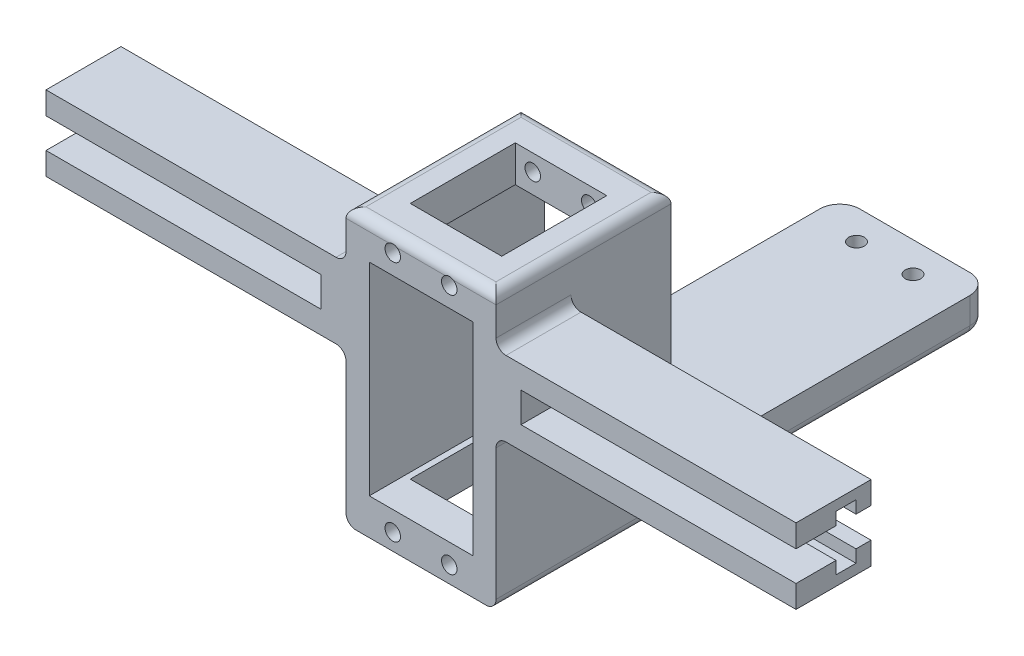
SolidWorks part; units mm, degrees
ref_plane "Front Plane" through (0, 0, 0) normal (0, 0, 1) x (1, 0, 0)
ref_plane "Top Plane" through (0, 0, 0) normal (0, 1, 0) x (1, 0, 0)
ref_plane "Right Plane" through (0, 0, 0) normal (1, 0, 0) x (0, 0, -1)
sketch "Sketch1" plane through (0, 0, 0) normal (0, 0, 1) x (1, 0, 0)
  line L0 (0, 15.3542) -> (0, -15.3542) construction
  line L1 (-15, 27.5) -> (15, 27.5)
  line L2 (-15, 27.5) -> (-15, -27.5)
  line L3 (-15, -27.5) -> (15, -27.5)
  line L4 (15, 27.5) -> (15, -27.5)
  line L5 (-15, 27.5) -> (15, -27.5) construction
  line L6 (-15, -27.5) -> (15, 27.5) construction
  line L7 (11.8315, 0) -> (-11.8315, 0) construction
  line L9 (-10.35, 20.25) -> (10.35, 20.25)
  line L10 (-10.35, 20.25) -> (-10.35, -20.25)
  line L11 (-10.35, -20.25) -> (10.35, -20.25)
  line L12 (10.35, 20.25) -> (10.35, -20.25)
  line L13 (-10.35, 20.25) -> (10.35, -20.25) construction
  line L14 (-10.35, -20.25) -> (10.35, 20.25) construction
  circle A0 centre (5.65, 24.2) radius 1.55
  circle A1 centre (-5.65, 24.2) radius 1.55
  circle A2 centre (-5.65, -24.2) radius 1.55
  circle A3 centre (5.65, -24.2) radius 1.55
  point P0 (0, 0)
  point P11 (0, 0)
  point P14 (0, 0)
  point P20 (0, 0)
  dimension "D3" = 3.1
  dimension "D5" = 11.3
  dimension "D1" = 55
  dimension "D2" = 30
  dimension "D4" = 24.2
  dimension "D6" = 62.6498
  dimension "D7" = 40.5
  dimension "D8" = 20.7
extrude "Boss-Extrude1" add sketch "Sketch1" along normal blind 35
sketch "Sketch4" plane through (0, 0, 0) normal (0, 0, -1) x (-1, 0, 0)
  line L0 (-15, 27.5) -> (15, 27.5) construction
  line L1 (9.15, 20.25) -> (-9.15, 20.25)
  line L2 (9.15, 20.25) -> (9.15, 27.5)
  line L3 (9.15, 27.5) -> (-9.15, 27.5)
  line L4 (-9.15, 20.25) -> (-9.15, 27.5)
  line L5 (-10.35, 20.25) -> (10.35, 20.25) construction
  line L7 (-5.65, 24.2) -> (-5.65, 21.212) construction
  circle A0 centre (5.65, 24.2) radius 1.55 construction
  point P0 (-5.65, 24.2)
  dimension "D1" = 3.5
  dimension "D2" = 3.5
extrude "Cut-Extrude1" [suppressed] cut sketch "Sketch4" against normal offset from surface (21 mm away) 7 from offset 7 offset against normal yes
pattern_linear "LPattern1" [suppressed] count 2 spacing 47.7 of bodies 102
sketch "Sketch11" plane through (0, 0, 0) normal (0, 0, -1) x (-1, 0, 0)
  line L0 (15, 27.5) -> (15, -27.5) construction
  line L1 (-15, -27.5) -> (15, -27.5)
  line L2 (-15, -27.5) -> (-15, -20.25)
  line L3 (-15, -20.25) -> (15, -20.25)
  line L4 (15, -27.5) -> (15, -20.25)
  line L5 (10.35, -20.25) -> (-10.35, -20.25) construction
extrude "Boss-Extrude5" add sketch "Sketch11" along normal blind 63.75
sketch "Sketch12" plane through (0, -27.5, 0) normal (0, -1, 0) x (1, 0, 0)
  line L0 (0, 0) -> (0, -63.75) construction
  line L1 (15, -63.75) -> (-15, -63.75) construction
  circle A0 centre (-5.65, -57.75) radius 1.55
  circle A1 centre (5.65, -57.75) radius 1.55
  dimension "D1" = 3.1
  dimension "D2" = 11.3
  dimension "D3" = 6
extrude "Cut-Extrude2" cut sketch "Sketch12" against normal blind 13
pattern_linear "LPattern2" count 2 spacing 48 along (0, 0, 1) of "Cut-Extrude2"
fillet "Fillet1" radius 4 4 edges at (-12.675, -20.25, 0) (12.675, -20.25, 0) (15, -23.875, -63.75) (-15, -23.875, -63.75)
sketch "Sketch13" plane through (0, 0, 35) normal (0, 0, 1) x (1, 0, 0)
  line L0 (-15, 10.25) -> (15, 10.25) construction
  line L1 (-15, -27.5) -> (15, -27.5) construction
  line L2 (-15, 27.5) -> (-15, -27.5) construction
  line L3 (-15, 27.5) -> (-15, -27.5)
  line L4 (15, -27.5) -> (15, 27.5) construction
  line L5 (0, 0) -> (0, 27.5) construction
  line L6 (-15, 2.75) -> (-75, 2.75)
  line L8 (-15, 17.75) -> (-75, 17.75)
  line L9 (-75, 2.75) -> (-75, 17.75)
  line L10 (-15, 10.25) -> (-75, 17.75) construction
  line L11 (-15, 10.25) -> (-75, 2.75) construction
  line L12 (15, 27.5) -> (-15, 27.5) construction
  line L13 (15, 2.75) -> (75, 2.75)
  line L14 (15, 10.25) -> (75, 2.75) construction
  line L15 (15, 10.25) -> (75, 17.75) construction
  line L16 (75, 2.75) -> (75, 17.75)
  line L17 (15, 17.75) -> (75, 17.75)
  line M12 (15, -27.5) -> (15, 27.5)
  dimension "D1" = 37.75
  dimension "D2" = 60
  dimension "D3" = 15
extrude "Boss-Extrude6" add sketch "Sketch13" against normal blind 15 contours L9 L6 L3 L8 | L17 L13 L16 M12 region at (-45, 10.25, 35) region at (45, 10.25, 35)
sketch "Sketch14" plane through (75, 0, 0) normal (1, 0, 0) x (0, 0, -1)
  line L0 (-35, 10.25) -> (-20, 10.25) construction
  line L1 (-35, 2.75) -> (-35, 17.75) construction
  line L2 (-20, 2.75) -> (-20, 17.75) construction
  line L3 (-35, 13.25) -> (-35, 7.25)
  line L4 (-35, 7.25) -> (-27, 7.25)
  line L5 (-27, 7.25) -> (-27, 4.75)
  line L6 (-27, 4.75) -> (-23, 4.75)
  line L8 (-27, 15.75) -> (-23, 15.75)
  line L9 (-27, 13.25) -> (-27, 15.75)
  line L10 (-35, 13.25) -> (-27, 13.25)
  line L11 (-23, 4.75) -> (-23, 7.25)
  line L12 (-23, 7.25) -> (-20, 7.25)
  line L13 (-20, 7.25) -> (-20, 13.25)
  line L14 (-23, 15.75) -> (-23, 13.25)
  line L15 (-23, 13.25) -> (-20, 13.25)
  point P13 (-23, 10.25)
  dimension "D1" = 6
  dimension "D2" = 8
  dimension "D3" = 4
  dimension "D4" = 11
extrude "Cut-Extrude3" cut sketch "Sketch14" against normal offset from surface (55 mm away) 5 up to face at (15, -1.5071, 5.2117)
sketch "Sketch15" plane through (0, 0, 35) normal (0, 0, 1) x (1, 0, 0)
  line L0 (0, 27.5) -> (0, 0) construction
  line L1 (15, 27.5) -> (-15, 27.5) construction
sketch "Sketch17" plane through (-75, 0, 0) normal (-1, 0, 0) x (0, 0, 1)
  line L0 (20, 10.25) -> (35, 10.25) construction
  line L1 (20, 17.75) -> (20, 2.75) construction
  line L2 (35, 27.5) -> (35, 0) construction
  line L3 (35, 7.25) -> (35, 13.25)
  line L4 (35, 2.75) -> (35, 17.75) construction
  line L5 (35, 13.25) -> (27, 13.25)
  line L6 (27, 13.25) -> (27, 15.75)
  line L7 (27, 15.75) -> (23, 15.75)
  line L9 (27, 4.75) -> (23, 4.75)
  line L10 (27, 7.25) -> (27, 4.75)
  line L11 (35, 7.25) -> (27, 7.25)
  line L12 (23, 15.75) -> (23, 13.25)
  line L13 (23, 13.25) -> (20, 13.25)
  line L14 (20, 13.25) -> (20, 7.25)
  line L15 (20, 7.25) -> (23, 7.25)
  line L16 (23, 7.25) -> (23, 4.75)
  point P15 (23, 10.25)
  dimension "D1" = 6
  dimension "D2" = 11
  dimension "D3" = 8
  dimension "D4" = 4
extrude "Cut-Extrude4" cut sketch "Sketch17" against normal offset from surface (55 mm away) 5 up to face at (-15, -1.5071, 5.2117)
sketch "Sketch18" plane through (0, 27.5, 0) normal (0, 1, 0) x (1, 0, 0)
  line L1 (-9.15, -7) -> (9.15, -7)
  line L2 (-9.15, -7) -> (-9.15, -28)
  line L3 (-9.15, -28) -> (9.15, -28)
  line L4 (9.15, -7) -> (9.15, -28)
  line L5 (-9.15, -7) -> (9.15, -28) construction
  line L6 (-9.15, -28) -> (9.15, -7) construction
  line L11 (15, -35) -> (-15, -35) construction
  point P0 (0, -17.5)
  dimension "D1" = 18.3
  dimension "D2" = 21
  dimension "D3" = 7
extrude "Cut-Extrude5" cut sketch "Sketch18" against normal through all
fillet "Fillet6" radius 2 6 edges at (15, 17.75, 27.5) (-15, 17.75, 27.5) (15, 27.5, 17.5) (-15, 27.5, 17.5) (0, 27.5, 35) (0, 27.5, 0)
fillet "Fillet7" radius 2 2 edges at (15, 2.75, 27.5) (-15, 2.75, 27.5)
fillet "Fillet8" radius 2 5 edges at (13.8284, -27.5, -62.5784) (0, -27.5, -63.75) (-13.8284, -27.5, -62.5784) (15, -27.5, -12.375) (-15, -27.5, -12.375)
